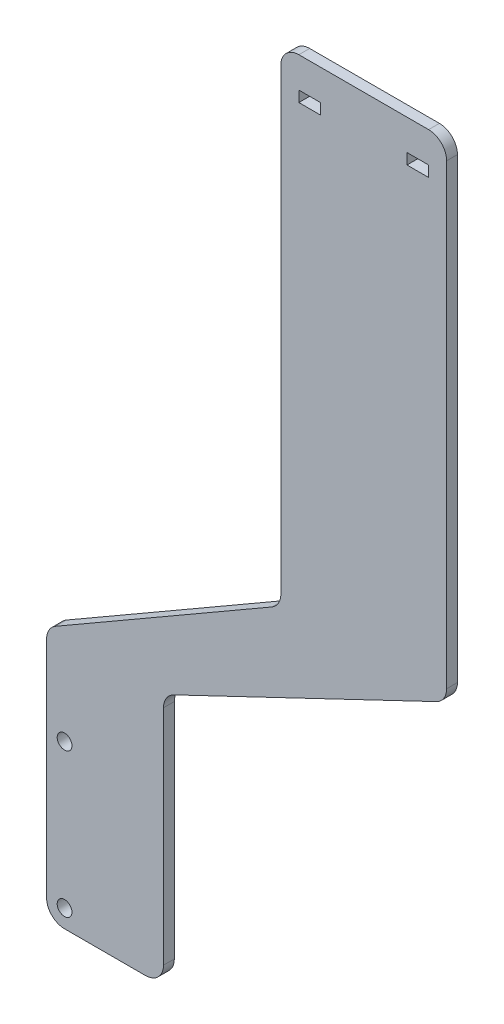
SolidWorks part; units mm, degrees
ref_plane "Front Plane" through (0, 0, 0) normal (0, 0, 1) x (1, 0, 0)
ref_plane "Top Plane" through (0, 0, 0) normal (0, 1, 0) x (1, 0, 0)
ref_plane "Right Plane" through (0, 0, 0) normal (1, 0, 0) x (0, 0, -1)
sketch "Sketch1" plane through (0, 0, 0) normal (0, 0, 1) x (1, 0, 0)
  line L0 (-78.6038, -75.5278) -> (-111.0529, -75.5278)
  line L1 (-111.0529, -75.5278) -> (-111.0529, -5.5278)
  line L3 (-46.0529, 32) -> (-46.0529, 167)
  line L4 (-46.0529, 167) -> (-0.0529, 167)
  line L5 (-0.0529, 167) -> (-0.0529, 32)
  line L6 (-106.0529, -30.5278) -> (-106.0529, -18.7631) construction
  line L7 (-23.0529, 167) -> (-23.0529, 157) construction
  line L8 (-23.0529, 157) -> (-1.1451, 157) construction
  line L9 (-35.0529, 158.5) -> (-35.0529, 155.5)
  line L10 (-11.0529, 158.5) -> (-5.0529, 158.5)
  line L11 (-11.0529, 158.5) -> (-11.0529, 155.5)
  line L12 (-11.0529, 155.5) -> (-5.0529, 155.5)
  line L13 (-5.0529, 158.5) -> (-5.0529, 155.5)
  line L14 (-11.0529, 158.5) -> (-5.0529, 155.5) construction
  line L15 (-11.0529, 155.5) -> (-5.0529, 158.5) construction
  line L16 (-35.0529, 155.5) -> (-41.0529, 155.5)
  line L17 (-41.0529, 158.5) -> (-41.0529, 155.5)
  line L18 (-35.0529, 158.5) -> (-41.0529, 158.5)
  line L19 (-46.0529, 32) -> (-111.0529, -5.5278)
  line L21 (-0.0529, 32) -> (-46.0529, 32) construction
  line L22 (-78.6038, -24.9561) -> (-78.6038, -75.5278)
  line L23 (-111.0529, -5.5278) -> (-78.6038, -5.5278) construction
  line L24 (-78.6038, -24.9561) -> (-78.6038, -5.5278)
  line L25 (-78.6038, -5.5278) -> (-0.0529, 32)
  circle A0 centre (-106.0529, -30.5278) radius 2.05
  circle A1 centre (-106.0529, -70.5278) radius 2.05
  point P15 (-8.0529, 157)
  dimension "D1" = 4.1
  dimension "D3" = 5
  dimension "D7" = 40
  dimension "D2" = 5
  dimension "D4" = 60
  dimension "D5" = 46
  dimension "D6" = 120
  dimension "D8" = 70
  dimension "D9" = 6
  dimension "D10" = 3
  dimension "D11" = 15
  dimension "D12" = 10
  dimension "D13" = 135
extrude "Boss-Extrude1" add sketch "Sketch1" along normal blind 3
fillet "Fillet1" radius 5 8 edges at (-46.0529, 167, 1.5) (-0.0529, 167, 1.5) (-111.0529, -75.5278, 1.5) (-46.0529, 32, 1.5) (-111.0529, -5.5278, 1.5) (-78.6038, -75.5278, 1.5) (-78.6038, -5.5278, 1.5) (-0.0529, 32, 1.5)
